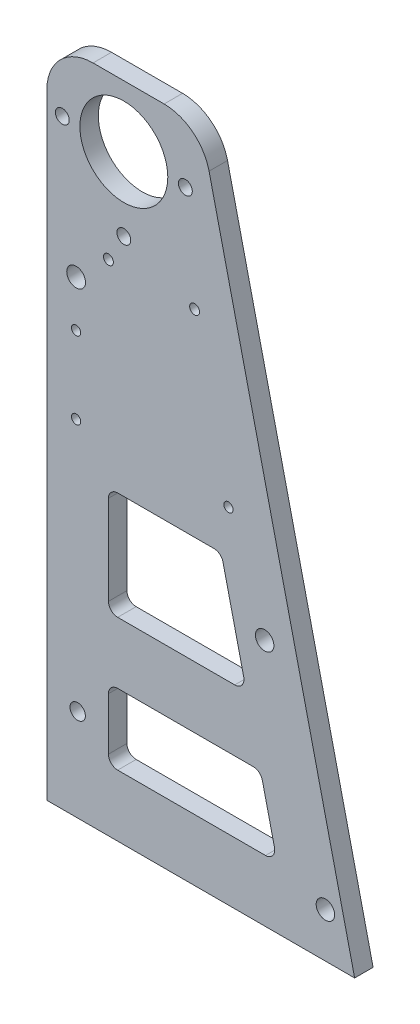
SolidWorks part; units mm, degrees
material "Policarbonato"
ref_plane "Plano frontal" through (0, 0, 0) normal (0, 0, 1) x (1, 0, 0)
ref_plane "Plano superior" through (0, 0, 0) normal (0, 1, 0) x (1, 0, 0)
ref_plane "Plano direito" through (0, 0, 0) normal (1, 0, 0) x (0, 0, -1)
sketch "Esboço1" plane through (0, 0, 0) normal (0, 0, 1) x (1, 0, 0)
  line L0 (0, 0) -> (0, 215)
  line L2 (100, 0) -> (0, 0)
  line L3 (0, 215) -> (50, 215)
  line L4 (50, 215) -> (100, 0)
  line L5 (10, 103) -> (10, 15) construction
  line L6 (25, 215) -> (25, 175) construction
  line L7 (10, 15) -> (75.7552, 15) construction
  line L8 (75.7552, 15) -> (55.2901, 103) construction
  line L9 (55.2901, 103) -> (10, 103) construction
  line L10 (20, 95) -> (20, 66)
  line L11 (23, 63) -> (61.0374, 63)
  line L12 (63.9594, 66.6795) -> (57.2152, 95.6795)
  line L13 (54.2932, 98) -> (23, 98)
  line L14 (20, 40) -> (20, 23)
  line L15 (23, 20) -> (71.0374, 20)
  line L16 (73.9594, 23.6795) -> (70.0059, 40.6795)
  line L17 (23, 43) -> (67.0839, 43)
  line L18 (0, 195) -> (50, 195) construction
  line L23 (17, 205) -> (33, 185) construction
  line L24 (17, 185) -> (33, 205) construction
  arc A8 (70.0059, 40.6795) -> (67.0839, 43) centre (67.0839, 40) ccw
  arc A9 (71.0374, 20) -> (73.9594, 23.6795) centre (71.0374, 23) ccw
  arc A10 (20, 23) -> (23, 20) centre (23, 23) ccw
  arc A11 (20, 40) -> (23, 43) centre (23, 40) cw
  arc A12 (57.2152, 95.6795) -> (54.2932, 98) centre (54.2932, 95) ccw
  arc A13 (61.0374, 63) -> (63.9594, 66.6795) centre (61.0374, 66) ccw
  arc A14 (20, 66) -> (23, 63) centre (23, 66) ccw
  arc A15 (20, 95) -> (23, 98) centre (23, 95) cw
  circle A20 centre (25, 195) radius 14.2875
  circle A21 centre (10, 30) radius 2.5
  point P8 (25, 195)
  point P49 (20, 63)
  dimension "D3" = 20
  dimension "D4" = 16
  dimension "D7" = 28.575
  dimension "D21" = 3
  dimension "D20" = 10
  dimension "D22" = 5
  dimension "D1" = 215
  dimension "D2" = 100
  dimension "D5" = 50
  dimension "D9" = 20
  dimension "D10" = 20
  dimension "D11" = 10
  dimension "D12" = 20
  dimension "D13" = 15
  dimension "D14" = 20
  dimension "D15" = 10
  dimension "D16" = 29
  dimension "D17" = 17
  dimension "D18" = 10
  dimension "D19" = 30
  dimension "D8" = 20
extrude "Ressalto-extrusão2" add sketch "Esboço1" along normal blind 6
fillet "Filete1" radius 15 2 edges at (0, 215, 3) (50, 215, 3)
sketch "Esboço3" plane through (0, 0, 0) normal (0, 0, -1) x (-1, 0, 0)
  line L1 (0, 0) -> (-100, 0) construction
  line L2 (0, 200) -> (0, 0) construction
  circle A0 centre (-9.5, 112) radius 1.5
  circle A1 centre (-90.5, 14.5) radius 3
  circle A2 centre (-9.5, 137) radius 1.5
  circle A3 centre (-9.5, 152) radius 3.05
  circle A4 centre (-59, 112) radius 1.5
  point P6 (-9.5, 112)
  point P9 (-9.5, 137)
  dimension "D5" = 6
  dimension "D1" = 25
  dimension "D6" = 3
  dimension "D7" = 112
  dimension "D8" = 15
  dimension "D9" = 6.1
  dimension "D10" = 49.5
  dimension "D2" = 9.5
  dimension "D3" = 14.5
  dimension "D4" = 9.5
extrude "Corte-extrusão1" cut sketch "Esboço3" against normal through all
sketch "Esboço5" plane through (0, 0, 0) normal (0, 0, -1) x (-1, 0, 0)
  line L0 (-45, 195) -> (-5, 195) construction
  circle A0 centre (-25, 171.1875) radius 2.25
  circle A1 centre (-70.7598, 80.3986) radius 3
  circle A2 centre (-25, 195) radius 14.2875 construction
  circle A3 centre (-20, 162.1875) radius 1.6
  circle A4 centre (-48, 162.1875) radius 1.6
  circle A5 centre (-45, 195) radius 2.25
  circle A6 centre (-5, 195) radius 2.25
  point P6 (-25, 195)
  point P17 (-2.75, 195)
  dimension "D1" = 23.8125
  dimension "D2" = 4.5
  dimension "D4" = 28
  dimension "D6" = 3.2
  dimension "D7" = 40
  dimension "D3" = 5
  dimension "D5" = 9
extrude "Corte-extrusão2" cut sketch "Esboço5" against normal through all
